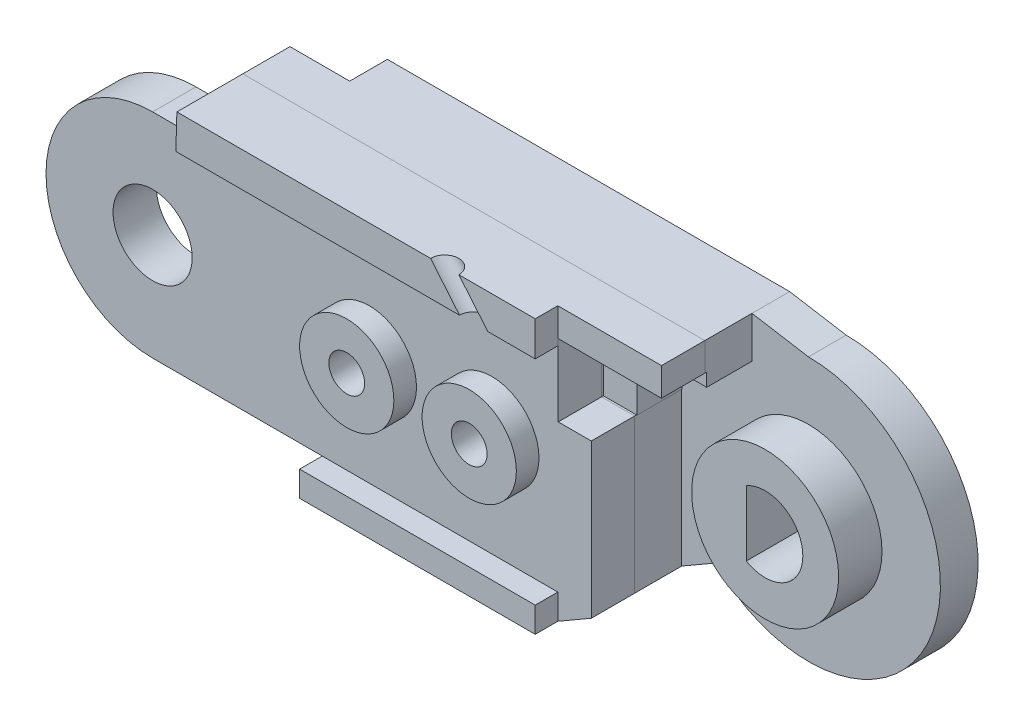
SolidWorks part; units mm, degrees
ref_plane "Front Plane" through (0, 0, 0) normal (0, 0, 1) x (1, 0, 0)
ref_plane "Top Plane" through (0, 0, 0) normal (0, 1, 0) x (1, 0, 0)
ref_plane "Right Plane" through (0, 0, 0) normal (1, 0, 0) x (0, 0, -1)
sketch "Sketch3" plane through (0, 0, 0) normal (0, 0, 1) x (1, 0, 0)
  line L7 (8, 0) -> (9, -2.5)
  line L11 (30, 7) -> (27, 7.5)
  line L13 (0, 7) -> (0, 7.5) construction
  line L14 (0, 7.5) -> (-22.3287, 7.5) construction
  line L15 (0, 5.3) -> (-14, 5.3) construction
  line L16 (0, 4) -> (-14, 4) construction
  line L17 (-14, 4) -> (-14, 5.3) construction
  line L18 (5.6569, 5.6569) -> (5.6569, 7.5)
  line L19 (5.6569, 7.5) -> (27, 7.5)
  line L20 (21.5, -7) -> (9, -7)
  line L21 (9, -7) -> (9, -2.5)
  line L23 (25.0503, -4.9497) -> (21.5, -7)
  arc A4 (8, 0) -> (5.6569, 5.6569) centre (0, 0) ccw
  arc A5 (25.0503, -4.9497) -> (30, 7) centre (30, 0) ccw
  circle A6 centre (0, 0) radius 7 construction
  circle A7 centre (0, 0) radius 3.9 construction
  circle A8 centre (0, 0) radius 5.3 construction
  circle A9 centre (0, 0) radius 4 construction
  dimension "D10" = 0.5
  dimension "D17" = 14
  dimension "D5" = 135
  dimension "D6" = 12.5
  dimension "D7" = 4.5
  dimension "D8" = 1
  dimension "D9" = 45
  dimension "D11" = 1.8431
  dimension "D12" = 30
  dimension "D14" = 3
extrude "Boss-Extrude1" add sketch "Sketch3" along normal blind 2 contours A5 L11 L19 L18 A4 L7 L21 L20 L23
sketch "Sketch20" plane through (0, 0, 0) normal (0, 0, 1) x (1, 0, 0)
  line L0 (0, 7) -> (0, 7.5) construction
  line L1 (0, 7.5) -> (-19.4737, 7.5) construction
  line L2 (0, 5.3) -> (-14, 5.3) construction
  line L3 (0, 4) -> (-14, 4) construction
  line L4 (-14, 4) -> (-14, 5.3) construction
  line L5 (0, 5.3) -> (17.4849, 5.3) construction
  line L6 (17.4849, 5.3) -> (17.4849, 4) construction
  line L7 (17.4849, 4) -> (0, 4) construction
  line L8 (-2.5, 7.5) -> (-2.5, 2.868) construction
  circle A0 centre (0, 0) radius 7 construction
  circle A1 centre (0, 0) radius 3.9 construction
  circle A3 centre (0, 0) radius 5.3 construction
  circle A4 centre (0, 0) radius 4 construction
  circle A5 centre (0, 0) radius 2 construction
  dimension "D1" = 0
  dimension "D2" = 2.5
ref_plane "Plane1" through (0, 0, 2) normal (0, 0, 1) x (1, 0, 0)
sketch "Sketch4" plane through (0, 0, 2) normal (0, 0, 1) x (1, 0, 0)
  line L4 (5.6569, 5.6569) -> (5.6569, 7.5)
  line L5 (5.6569, 5.6569) -> (5.6569, 7.5) construction
  line L6 (5.6569, 7.5) -> (21.5, 7.5)
  line L10 (8, 0) -> (9, -2.5)
  line L11 (9, -2.5) -> (9, -7)
  line L12 (9, -7) -> (21.5, -7)
  line L13 (21.5, -7) -> (21.5, 7.5)
  arc A0 (8, 0) -> (5.6569, 5.6569) centre (0, 0) ccw construction
  arc A3 (8, 0) -> (5.6569, 5.6569) centre (0, 0) ccw
sketch "Sketch22" plane through (0, 0, 2) normal (0, 0, 1) x (1, 0, 0)
  line L0 (5.6569, 5.6569) -> (2.4868, 5.6569)
  line L1 (5.6569, 7.5) -> (21.5, 7.5)
  line L2 (5.6569, 7.5) -> (2.4868, 7.5)
  line L3 (2.4868, 7.5) -> (2.4868, 5.6569)
  line L6 (8, 0) -> (9, -2.5)
  line L7 (9, -2.5) -> (9, -7)
  line L8 (9, -7) -> (21.5, -7)
  line L10 (21.5, 7.5) -> (27, 7.5)
  line L11 (27, 7.5) -> (27, 2.172)
  line L12 (27, 2.172) -> (23.2751, 2.172)
  line L13 (21.5, -7) -> (23.2751, -5.9749)
  line L14 (25.0503, -4.9497) -> (21.5, -7) construction
  line L15 (23.2751, -5.9749) -> (23.2751, 2.172)
  arc A0 (8, 0) -> (5.6569, 5.6569) centre (0, 0) ccw
extrude "Boss-Extrude6" add sketch "Sketch22" along normal blind 2.5
sketch "Sketch25" plane through (0, 0, 2) normal (0, 0, 1) x (1, 0, 0)
  line L0 (0, 5.3) -> (18.0981, 5.3) construction
  line L1 (0, 4) -> (18.0981, 4) construction
  line L2 (18.0981, 4) -> (18.0981, 5.3) construction
sketch "Sketch26" plane through (0, 0, 2) normal (0, 0, 1) x (1, 0, 0)
  line L1 (18.0981, 5.3) -> (2.5301, 5.3)
  line L2 (18.0981, 4) -> (2.5301, 4)
  line L3 (2.5301, 5.3) -> (2.5301, 4)
  line L4 (18.0981, 5.3) -> (27, 5.3)
  line L5 (27, 2.172) -> (27, 7.5) construction
  line L6 (27, 5.3) -> (27, 4)
  line L7 (27, 4) -> (18.0981, 4)
extrude "Cut-Extrude6" cut sketch "Sketch26" along normal blind 2.5
ref_plane "Plane18" through (0, 0, 4.5) normal (0, 0, 1) x (1, 0, 0)
sketch "Sketch31" plane through (0, 0, 4.5) normal (0, 0, 1) x (1, 0, 0)
  line L0 (2.4327, 5.6569) -> (0, 5.6569)
  line L4 (9, -5.6569) -> (0, -5.6569)
  line L5 (2.4327, 5.6569) -> (2.4868, 7.5)
  line L12 (9, -7) -> (9, -5.6569)
  line L13 (9, -2.5) -> (9, -7) construction
  line L16 (27, 7.5) -> (27, 2.172)
  line L17 (27, 2.172) -> (23.2751, 2.172)
  line L18 (23.2751, -5.9749) -> (23.2751, 2.172)
  line L19 (27, 7.5) -> (2.4868, 7.5)
  line L20 (9, -7) -> (21.5, -7)
  line L21 (21.5, -7) -> (23.2751, -5.9749)
  arc A0 (0, 5.6569) -> (0, -5.6569) centre (0, 0) ccw
  dimension "D1" = 5.6569
extrude "Boss-Extrude14" add sketch "Sketch31" along normal blind 2.3 separate body
sketch "Sketch32" plane through (0, 0, 6.8) normal (0, 0, 1) x (1, 0, 0)
  circle A0 centre (0, 0) radius 2.1
extrude "Cut-Extrude7" cut sketch "Sketch32" against normal blind 2.3
sketch "Sketch33" plane through (0, 0, 6.8) normal (0, 0, 1) x (1, 0, 0)
  line L4 (9, -5.6569) -> (9, -7)
  line L11 (9, -7) -> (21.5, -7)
  line L15 (21.5, -7) -> (21.5, -5.6569)
  line L16 (21.5, -5.6569) -> (9, -5.6569)
  line L17 (2.4868, 7.5) -> (21.5, 7.5)
  line L18 (27, 7.5) -> (2.4868, 7.5) construction
  line L19 (2.4868, 7.5) -> (2.4327, 5.6569)
  line L20 (2.4327, 5.6569) -> (21.5, 5.6569)
  line L21 (21.5, 5.6569) -> (21.5, 7.5)
extrude "Boss-Extrude15" add sketch "Sketch33" along normal blind 1.2
sketch "Sketch34" plane through (0, 0, 2) normal (0, 0, 1) x (1, 0, 0)
  line L0 (30, 5.3) -> (18.0981, 5.3) construction
  line L1 (30, 4) -> (18.0981, 4) construction
  circle A0 centre (30, 0) radius 2 construction
  circle A1 centre (30, 0) radius 5.3 construction
  circle A2 centre (30, 0) radius 4 construction
sketch "Sketch35" plane through (0, 0, 6.8) normal (0, 0, 1) x (1, 0, 0)
  line L0 (27, 2.172) -> (27, 6)
  line L1 (27, 2.172) -> (21.5204, 2.172)
  line L2 (27, 6) -> (21.5204, 6)
  line L3 (21.5204, 2.172) -> (21.5204, 6)
  line L4 (27, 2.172) -> (27, 7.5) construction
extrude "Cut-Extrude8" cut sketch "Sketch35" against normal blind 2.4
sketch "Sketch36" plane through (0, 0, 4.4) normal (0, 0, 1) x (1, 0, 0)
  line L0 (27, 2.172) -> (27, 4)
  line L1 (27, 2.172) -> (23.3, 2.172)
  line L2 (27, 4) -> (23.3, 4)
  line L3 (23.3, 2.172) -> (23.3, 4)
  line L4 (21.5, -7) -> (21.5, 7.5) construction
  dimension "D1" = 1.8
extrude "Cut-Extrude9" cut sketch "Sketch36" against normal blind 2.4
sketch "Sketch37" plane through (0, 0, 2) normal (0, 0, 1) x (1, 0, 0)
  circle A0 centre (30, 0) radius 3.9
extrude "Boss-Extrude16" add sketch "Sketch37" along normal blind 2.3
sketch "Sketch39" plane through (0, 0, 4.3) normal (0, 0, 1) x (1, 0, 0)
  line L0 (29, 1.7321) -> (29, -1.7321)
  arc A0 (29, -1.7321) -> (29, 1.7321) centre (30, 0) ccw
  dimension "D2" = 4
  dimension "D1" = 1
extrude "Cut-Extrude10" cut sketch "Sketch39" against normal through all
sketch "Sketch43" plane through (0, 0, 6.8) normal (0, 0, 1) x (1, 0, 0)
  line L2 (0, -5.6569) -> (9, -5.6569) construction
  circle A0 centre (11.5, 0) radius 2.5
  circle A1 centre (18, 0) radius 2.5
  dimension "D1" = 2.5
  dimension "D3" = 5
  dimension "D4" = 6.5
  dimension "D2" = 5.6569
extrude "Boss-Extrude17" add sketch "Sketch43" along normal blind 1.2
sketch "Sketch44" plane through (0, 0, 8) normal (0, 0, 1) x (1, 0, 0)
  circle A0 centre (11.5, 0) radius 0.95
  circle A1 centre (18, 0) radius 0.95
  dimension "D1" = 1.9
  dimension "D2" = 1.9
extrude "Cut-Extrude11" cut sketch "Sketch44" against normal through all
sketch "Sketch45" plane through (0, 0, 0) normal (0, 0, -1) x (-1, 0, 0)
  circle A0 centre (-11.5, 0) radius 2
  circle A1 centre (-18, 0) radius 2
extrude "Cut-Extrude12" cut sketch "Sketch45" against normal blind 2.5
ref_plane "Plane17" through (0, 0, 8) normal (0, 0, 1) x (1, 0, 0)
sketch "Sketch48" plane through (0, 0, 2) normal (0, 0, 1) x (1, 0, 0)
  circle A0 centre (30, 0) radius 5 construction
sketch "Sketch51" plane through (0, 0, 8) normal (0, 0, 1) x (1, 0, 0)
  line L0 (18.2355, 5.6569) -> (27.0112, -4.8677) construction
  line L1 (2.4327, 5.6569) -> (21.5, 5.6569) construction
sketch "Sketch52" plane through (0, 5.6569, 0) normal (0, -1, 0) x (1, 0, 0)
  circle A0 centre (18.2355, 8) radius 0.75
extrude "Cut-Extrude13" cut sketch "Sketch52" along direction (0.6404, -0.768, 0) on the side against the normal blind 10
